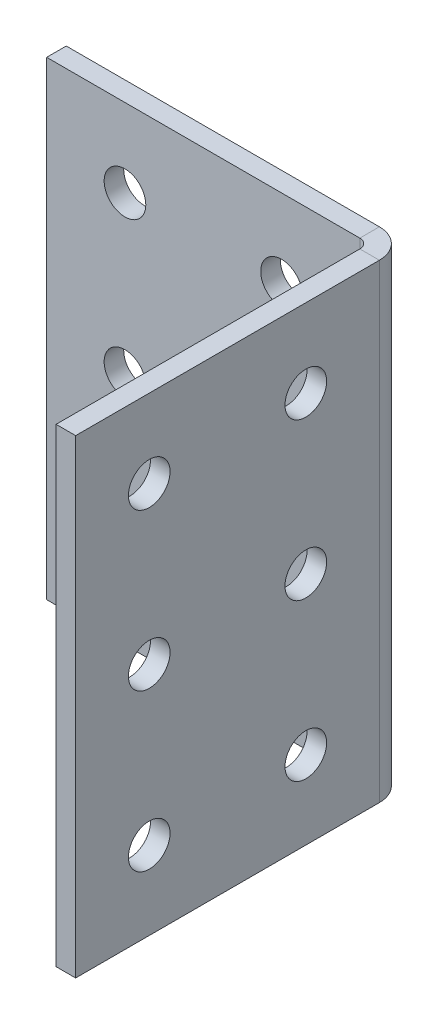
SolidWorks part; units mm, degrees
note: The reader was unsure of these and kept them because the rebuilt part matched: flange length of "Edge-Flange1".
material "6061-T6 (SS)"
ref_plane "Front" through (0, 0, 0) normal (0, 0, 1) x (1, 0, 0)
ref_plane "Top" through (0, 0, 0) normal (0, 1, 0) x (1, 0, 0)
ref_plane "Right" through (0, 0, 0) normal (1, 0, 0) x (0, 0, -1)
sketch "Sketch1" plane through (0, 0, 0) normal (0, 0, 1) x (1, 0, 0)
  line L1 (0, 0) -> (50.8, 0)
  line L2 (0, 0) -> (0, 76.2)
  line L3 (0, 76.2) -> (50.8, 76.2)
  line L4 (50.8, 0) -> (50.8, 76.2)
  dimension "D1" = 76.2
  dimension "D2" = 50.8
base flange "Base-Flange1" sketch "Sketch1" thickness 3.175 reverse thickness direction no parameters "D1"=1.524
edge flange "Edge-Flange1" sketch "Sketch8" flange angle 90 flange length 50.8 flange position bend outside bend radius 1.524 thickness 3.175 relief rectangular parameters "D6"=10
sketch "Sketch8" plane through (50.8, 0, 0) normal (1, 0, 0) x (0, 1, 0)
  line L2 (0, 0) -> (0, 50.8)
  line L3 (0, 50.8) -> (76.2, 50.8)
  line L4 (76.2, 50.8) -> (76.2, 0)
  line L7 (0, 0) -> (76.2, 0) construction
  line L8 (0, 0) -> (76.2, 0)
bend "EdgeBend1" bend radius 1.524 bend angle 90 parameters "D5"=1
hole_wizard "1/4 Clearance Hole1" positions "Sketch9" profile "Sketch10" hole size "1/4" standard "ANSI Inch" end condition up to next
sketch "Sketch9" plane through (0, 0, 0) normal (0, 0, 1) x (1, 0, 0)
  line L2 (38.1, 63.5) -> (0, 63.5) construction
  line L3 (0, 76.2) -> (0, 0) construction
  line L5 (12.7, 63.5) -> (50.8, 63.5) construction
  line L6 (50.8, 76.2) -> (50.8, 0) construction
  line L7 (25.4, 76.2) -> (25.4, 63.5) construction
  line L8 (50.8, 76.2) -> (0, 76.2) construction
  line L10 (12.7, 12.7) -> (12.7, 0) construction
  line L11 (0, 0) -> (50.8, 0) construction
  point P0 (38.1, 63.5)
  point P2 (12.7, 63.5)
  point P4 (12.7, 38.1)
  point P6 (38.1, 38.1)
  point P8 (12.7, 12.7)
  point P10 (38.1, 12.7)
  dimension "D1" = 25.4
  dimension "D2" = 25.4
  dimension "D3" = 25.4
sketch "Sketch10" plane through (38.1, 63.5, 0) normal (1, 0, 0) x (0, -1, 0)
  line L0 (0, 0) -> (0, 3.175)
  line L1 (0, 3.175) -> (3.3782, 3.175)
  line L2 (3.3782, 3.175) -> (3.3782, 0)
  line L5 (3.3782, 0) -> (0, 0)
  line L11 (0, -6.35) -> (0, 107.95) construction
  dimension "Thru Hole Dia." = 6.7564
  dimension "Thru Hole Depth" = 3.175
hole_wizard "1/4 Clearance Hole2" positions "Sketch11" profile "Sketch12" hole size "1/4" standard "ANSI Inch" end condition up to next
sketch "Sketch11" plane through (52.324, 0, 0) normal (-1, 0, 0) x (0, 0, 1)
  line L0 (38.862, 63.5) -> (38.862, 76.2) construction
  line L1 (1.524, 76.2) -> (50.8, 76.2) construction
  line L3 (38.862, 12.7) -> (38.862, 0) construction
  line L4 (50.8, 0) -> (1.524, 0) construction
  line L6 (13.462, 38.1) -> (1.524, 38.1) construction
  line L7 (1.524, 0) -> (1.524, 76.2) construction
  line L9 (38.862, 38.1) -> (50.8, 38.1) construction
  line L10 (50.8, 76.2) -> (50.8, 0) construction
  point P0 (13.462, 63.5)
  point P2 (38.862, 63.5)
  point P4 (13.462, 38.1)
  point P6 (38.862, 38.1)
  point P8 (13.462, 12.7)
  point P10 (38.862, 12.7)
  dimension "D1" = 25.4
  dimension "D2" = 25.4
  dimension "D3" = 25.4
sketch "Sketch12" plane through (52.324, 63.5, 13.462) normal (0, 1, 0) x (0, 0, 1)
  line L0 (0, 0) -> (0, 3.175)
  line L1 (0, 3.175) -> (3.3782, 3.175)
  line L2 (3.3782, 3.175) -> (3.3782, 0)
  line L5 (3.3782, 0) -> (0, 0)
  line L11 (0, -6.35) -> (0, 107.95) construction
  dimension "Thru Hole Dia." = 6.7564
  dimension "Thru Hole Depth" = 3.175
sketch "Bend-Lines1" [suppressed] plane through (0, 0, 0) normal (0, 1, 0) x (1, 0, 0)
sketch "Bounding-Box1" [suppressed] plane through (0, 0, 0) normal (0, 1, 0) x (1, 0, 0)
sheet metal parameters "Sheet-Metal8" thickness 3.175 parameters "D1"=1.524
flat pattern "Flat-Pattern8" [suppressed]
sketch "Bend-Lines2" plane through (0, 0, 0) normal (0, 1, 0) x (1, 0, 0)
sketch "Bounding-Box2" [suppressed] plane through (0, 0, 0) normal (0, 1, 0) x (1, 0, 0)
sheet metal parameters "Sheet-Metal9" thickness 3.175 parameters "D1"=1.524
flat pattern "Flat-Pattern8" [suppressed]
sketch "Bend-Lines2" plane through (0, 0, 0) normal (0, 1, 0) x (1, 0, 0)
sketch "Bounding-Box2" [suppressed] plane through (0, 0, 0) normal (0, 1, 0) x (1, 0, 0)
bend of the flat pattern "Flatten-<EdgeBend1>1"
sheet metal parameters "Sheet-Metal10" thickness 3.175 parameters "D1"=1.524
flat pattern "Flat-Pattern8" [suppressed]
sketch "Bend-Lines2" plane through (0, 0, 0) normal (0, 1, 0) x (1, 0, 0)
sketch "Bounding-Box2" [suppressed] plane through (0, 0, 0) normal (0, 1, 0) x (1, 0, 0)
bend of the flat pattern "Flatten-<EdgeBend1>1"
sheet metal parameters "Sheet-Metal11" thickness 3.175 parameters "D1"=1.524
flat pattern "Flat-Pattern8"
sketch "Bend-Lines2" plane through (0, 0, 0) normal (0, 0, 1) x (1, 0, 0)
  line L0 (53.2438, 0) -> (53.2438, 76.2) construction
  line L1 (53.2438, 0) -> (53.2438, 76.2) construction
sketch3d "Bounding-Box2" [suppressed]
  line L0 (0, 0, 0) -> (104.9635, 0, 0) construction
  line L1 (0, 76.2, 0) -> (104.9635, 76.2, 0) construction
  line L2 (0, 0, 0) -> (0, 76.2, 0) construction
  line L3 (104.9635, 0, 0) -> (104.9635, 76.2, 0) construction
bend of the flat pattern "Flatten-<EdgeBend1>1"
